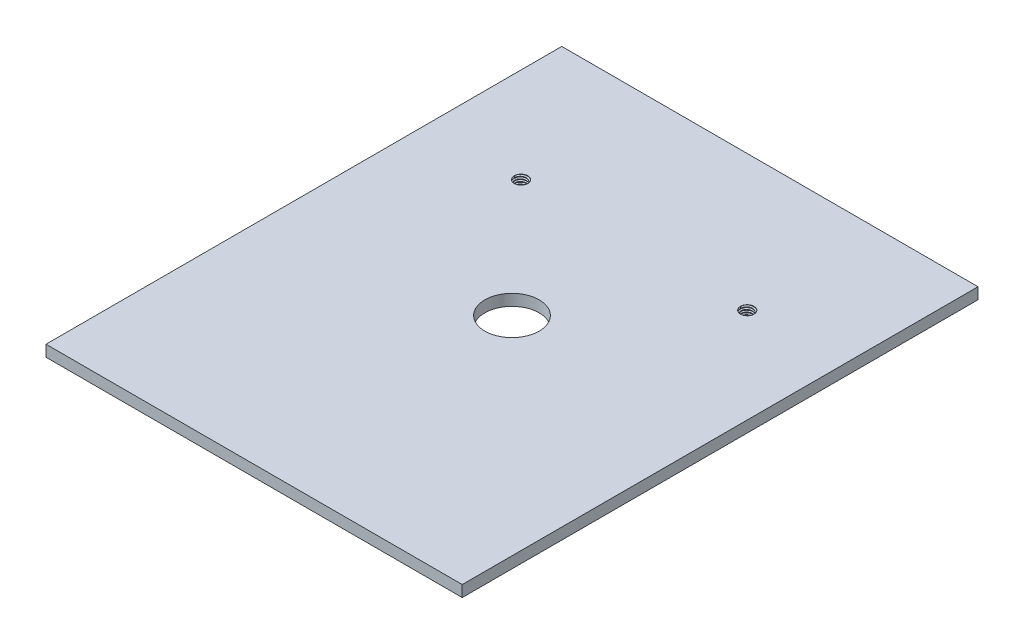
SolidWorks part; units mm, degrees
ref_plane "Front Plane" through (0, 0, 0) normal (0, 0, 1) x (1, 0, 0)
ref_plane "Top Plane" through (0, 0, 0) normal (0, 1, 0) x (1, 0, 0)
ref_plane "Right Plane" through (0, 0, 0) normal (1, 0, 0) x (0, 0, -1)
sketch "Sketch1" plane through (0, 0, 0) normal (0, 1, 0) x (1, 0, 0)
  line L1 (-92, 114) -> (92, 114)
  line L2 (-92, 114) -> (-92, -114)
  line L3 (-92, -114) -> (92, -114)
  line L4 (92, 114) -> (92, -114)
  line L5 (-92, 114) -> (92, -114) construction
  line L6 (-92, -114) -> (92, 114) construction
  point P0 (0, 0)
  dimension "D1" = 228
  dimension "D2" = 184
extrude "Boss-Extrude1" add sketch "Sketch1" along normal blind 5
sketch "Sketch2" plane through (0, 5, 0) normal (0, 1, 0) x (1, 0, 0)
  circle A0 centre (-50, 54) radius 3
  circle A1 centre (50, 54) radius 3
  circle A2 centre (0, 0) radius 12
  dimension "D1" = 60
  dimension "D3" = 6
  dimension "D4" = 60
  dimension "D6" = 6
  dimension "D7" = 24
  dimension "D2" = 50
  dimension "D5" = 50
extrude "Cut-Extrude1" cut sketch "Sketch2" against normal through all
thread "Thread2" pitch 1 method extrude profile "Thread Profile3" start angle 0, offset 0, length 10, pitch 1, diameter 6
ref_plane "Plane3" through (-53, 5, -54) normal (0, 0, 1) x (-1, 0, 0)
sketch "Thread Profile3" plane through (-53, 5, -54) normal (0, 0, 1) x (-1, 0, 0)
  line L0 (0, 0) -> (0, 1) construction
  line L11 (0, 0) -> (0, 0.875)
  line L12 (0, 0.875) -> (-0.5413, 0.5625)
  line L13 (-0.5413, 0.5625) -> (-0.5413, 0.3125)
  line L15 (-0.5413, 0.3125) -> (0, 0)
  line L17 (-0.5413, 0.4375) -> (0, 0.4375) construction
  point P2 (0, 0)
  dimension "Pitch" = 1
  dimension "Profile_Angle" = 60
  dimension "Profile_Land" = 0.25
  dimension "Profile_Height" = 0.5413
thread "Thread3" pitch 1 method extrude profile "Thread Profile4" start angle 0, offset 0, length 10, pitch 1, diameter 6
ref_plane "Plane4" through (47, 5, -54) normal (0, 0, 1) x (-1, 0, 0)
sketch "Thread Profile4" plane through (47, 5, -54) normal (0, 0, 1) x (-1, 0, 0)
  line L0 (0, 0) -> (0, 1) construction
  line L11 (0, 0) -> (0, 0.875)
  line L12 (0, 0.875) -> (-0.5413, 0.5625)
  line L13 (-0.5413, 0.5625) -> (-0.5413, 0.3125)
  line L15 (-0.5413, 0.3125) -> (0, 0)
  line L17 (-0.5413, 0.4375) -> (0, 0.4375) construction
  point P2 (0, 0)
  dimension "Pitch" = 1
  dimension "Profile_Angle" = 60
  dimension "Profile_Land" = 0.25
  dimension "Profile_Height" = 0.5413
sketch "Sketch3" plane through (0, 0, 0) normal (1, 0, 0) x (0, 0, -1)
  line L0 (-114, 0) -> (114, 0) construction
  line L1 (50.549, -6) -> (57.4031, -6)
  line L2 (50.549, -6) -> (50.549, 0)
  line L3 (50.549, 0) -> (57.4031, 0)
  line L4 (57.4031, -6) -> (57.4031, 0)
  dimension "D1" = 6
  dimension "D2" = 6.8541
extrude "Cut-Extrude2" cut sketch "Sketch3" against normal through all both and the other way through all
